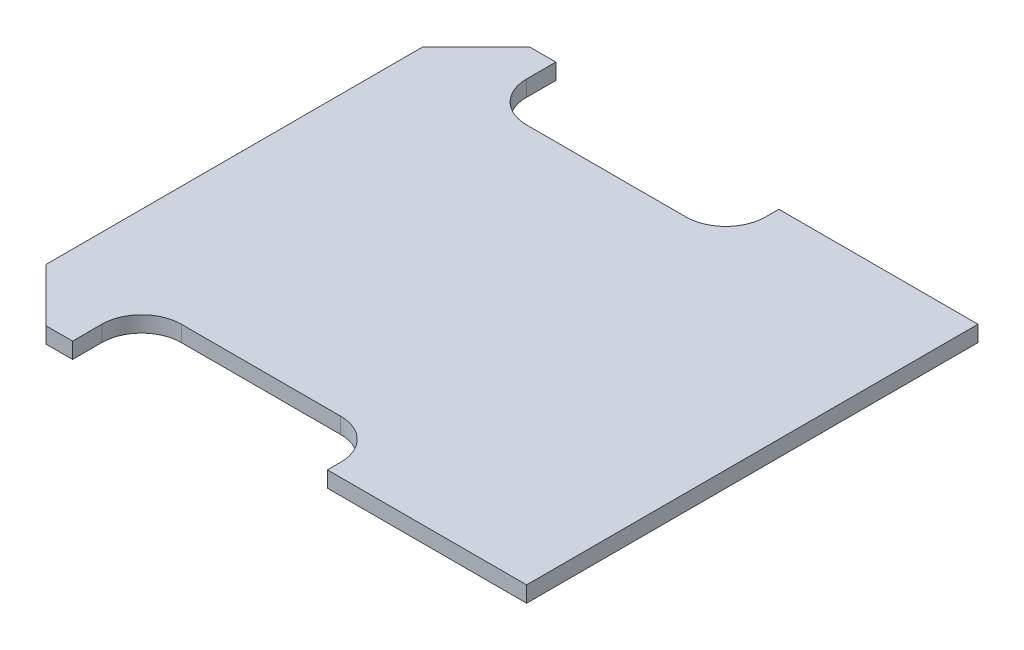
SolidWorks part; units mm, degrees
material "ABS"
ref_plane "Front Plane" through (0, 0, 0) normal (0, 0, 1) x (1, 0, 0)
ref_plane "Top Plane" through (0, 0, 0) normal (0, 1, 0) x (1, 0, 0)
ref_plane "Right Plane" through (0, 0, 0) normal (1, 0, 0) x (0, 0, -1)
sketch "Sketch1" plane through (0, 0, 0) normal (0, 1, 0) x (1, 0, 0)
  line L1 (-97.5, 85) -> (97.5, 85)
  line L2 (-97.5, 85) -> (-97.5, -85)
  line L3 (-97.5, -85) -> (97.5, -85)
  line L4 (97.5, 85) -> (97.5, -85)
  line L5 (-97.5, 85) -> (97.5, -85) construction
  line L6 (-97.5, -85) -> (97.5, 85) construction
  point P0 (0, 0)
  dimension "D1" = 195
  dimension "D2" = 170
extrude "Boss-Extrude1" add sketch "Sketch1" along normal blind 6
sketch "Sketch2" plane through (0, 6, 0) normal (0, 1, 0) x (1, 0, 0)
  line L0 (-97.5, -85) -> (-67.5, -85) construction
  line L1 (-97.5, -85) -> (97.5, -85) construction
  line L2 (0, 0) -> (-97.5, 0) construction
  line L3 (-67.5, -85) -> (22.5, -85)
  line L4 (-67.5, -85) -> (-67.5, -65)
  line L5 (-67.5, -65) -> (22.5, -65)
  line L6 (22.5, -85) -> (22.5, -65)
  line L7 (-97.5, 85) -> (-97.5, -85) construction
  line L8 (-67.5, 65) -> (22.5, 65)
  line L9 (22.5, 85) -> (22.5, 65)
  line L10 (-67.5, 85) -> (22.5, 85)
  line L11 (-67.5, 85) -> (-67.5, 65)
  dimension "D1" = 30
  dimension "D2" = 90
  dimension "D3" = 20
extrude "Cut-Extrude1" cut sketch "Sketch2" against normal through all
fillet "Fillet1" radius 15 4 edges at (22.5, 3, -65) (-67.5, 3, -65) (-67.5, 3, 65) (22.5, 3, 65)
sketch "Sketch3" plane through (0, 6, 0) normal (0, 1, 0) x (1, 0, 0)
  line L0 (0, 0) -> (-97.5, 0) construction
  line L1 (-67.5, 85) -> (-97.5, 85)
  line L2 (-67.5, 85) -> (-67.5, 91)
  line L3 (-67.5, 91) -> (-97.5, 91)
  line L4 (-97.5, 85) -> (-97.5, 91)
  line L5 (-97.5, 85) -> (-97.5, -85) construction
  line L6 (-67.5, -91) -> (-97.5, -91)
  line L7 (-97.5, -85) -> (-97.5, -91)
  line L8 (-67.5, -85) -> (-97.5, -85)
  line L9 (-67.5, -85) -> (-67.5, -91)
  dimension "D1" = 6
extrude "Boss-Extrude2" add sketch "Sketch3" against normal up to surface (6 mm away) up to face at (-16.875, 0, 0)
chamfer "Chamfer1" distance 20 angle 45 2 edges at (-97.5, 3, 91) (-97.5, 3, -91)
